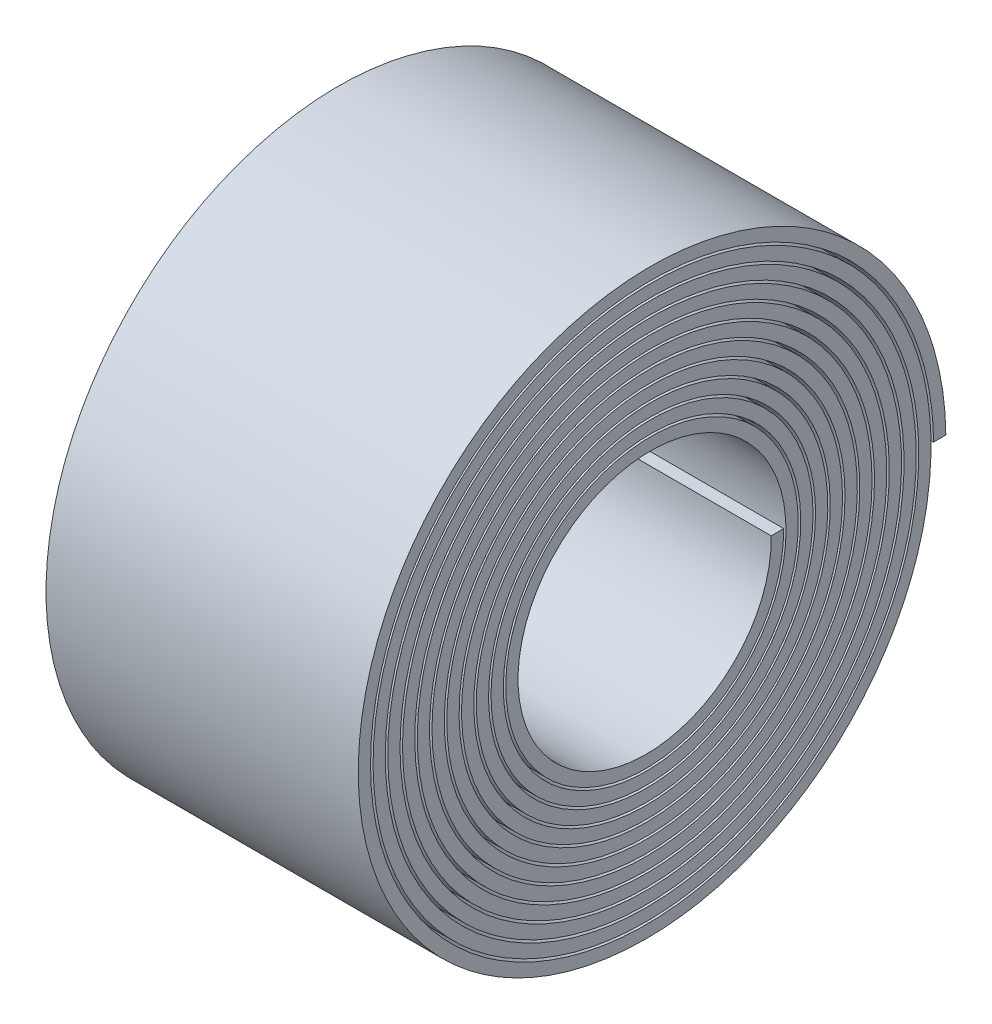
SolidWorks part; units mm, degrees
ref_plane "Front Plane" through (0, 0, 0) normal (0, 0, 1) x (1, 0, 0)
ref_plane "Top Plane" through (0, 0, 0) normal (0, 1, 0) x (1, 0, 0)
ref_plane "Right Plane" through (0, 0, 0) normal (1, 0, 0) x (0, 0, -1)
sketch "Sketch1" plane through (0, 0, 0) normal (1, 0, 0) x (0, 0, -1)
  circle A0 centre (0, 0) radius 2.5
  dimension "D1" = 5
curve "Helix/Spiral1"
sketch "Sketch2" plane through (0, 0, 0) normal (1, 0, 0) x (0, 0, -1)
  line L0 (2.5, 0) -> (2.75, 0.0048)
  line L2 (5.8, 0) -> (6.05, 0.0021)
  spline S0 degree 3 poles (-421.9366, -905.3575) (-57.6424, 57.3436) (7.9155, 8.7178) (1.9401, -1.6929) (1.6038, -2.0262) (0.8018, -2.4743) (0.3373, -2.5884) (-0.5902, -2.5601) (-1.0519, -2.4176) (-1.8406, -1.9113) (-2.1664, -1.5481) (-2.5866, -0.6999) (-2.6802, -0.2161) (-2.6036, 0.7366) (-2.4335, 1.2041) (-1.8725, 1.9894) (-1.4824, 2.3059) (-0.5889, 2.6946) (-0.0868, 2.7661) (0.8885, 2.6388) (1.3604, 2.4401) (2.1387, 1.8236) (2.444, 1.4066) (2.7978, 0.4689) (2.8456, -0.0505) (2.6652, -1.0457) (2.437, -1.5201) (1.7644, -2.2878) (1.3208, -2.58) (0.3402, -2.8954) (-0.1953, -2.9181) (-1.2075, -2.6823) (-1.6827, -2.424) (-2.4362, -1.6949) (-2.7134, -1.2249) (-2.9871, -0.203) (-2.9831, 0.3474) (-2.6898, 1.3734) (-2.4008, 1.8476) (-1.6149, 2.5831) (-1.119, 2.8434) (-0.0577, 3.072) (0.5063, 3.0399) (1.5429, 2.6873) (2.0141, 2.3671) (2.7278, 1.5245) (2.9693, 1.0032) (3.1497, -0.0956) (3.0882, -0.6716) (2.6745, -1.7154) (2.3227, -2.1817) (1.4237, -2.8698) (0.8778, -3.0906) (-0.2563, -3.2195) (-0.8428, -3.1274) (-1.8902, -2.651) (-2.3496, -2.2674) (-3.0082, -1.3126) (-3.2065, -0.7428) (-3.281, 0.4241) (-3.1571, 1.0194) (-2.6168, 2.0667) (-2.2011, 2.5172) (-1.1912, 3.1425) (-0.5985, 3.3164) (0.5985, 3.3336) (1.2009, 3.1767) (2.2444, 2.5714) (2.6838, 2.1236) (3.2719, 1.0598) (3.4197, 0.4451) (3.3768, -0.779) (3.186, -1.3868) (2.5147, -2.4224) (2.035, -2.8487) (0.9184, -3.3959) (0.2831, -3.5158) (-0.9652, -3.4101) (-1.5763, -3.1846) (-2.6001, -2.4467) (-3.0113, -1.9353) (-3.5136, -0.7674) (-3.604, -0.1126) (-3.4331, 1.1565) (-3.172, 1.769) (-2.3671, 2.7768) (-1.8243, 3.1707) (-0.6071, 3.6246) (0.0658, 3.6837) (1.3523, 3.4454) (1.9641, 3.148) (2.9519, 2.276) (3.3264, 1.7023) (3.728, 0.4376) (3.7545, -0.2517) (3.4465, -1.552) (3.1124, -2.1611) (2.1732, -3.1246) (1.5694, -3.4776) (0.2594, -3.8234) (-0.4448, -3.8157) (-1.755, -3.4362) (-2.3591, -3.0649) (-3.2941, -2.0589) (-3.6235, -1.4256) (-3.9101, -0.073) (-3.8667, 0.6444) (-3.414, 1.9607) (-3.0053, 2.5576) (-1.9331, 3.4598) (-1.2712, 3.7636) (0.1214, 3.9875) (0.8501, 3.9072) (2.1683, 3.3799) (2.7558, 2.9334) (3.6209, 1.7959) (3.897, 1.1064) (4.0551, -0.3232) (3.9367, -1.0613) (3.3334, -2.3772) (2.8492, -2.953) (1.6475, -3.7767) (0.9316, -4.0232) (-0.5319, -4.1123) (-1.2774, -3.9547) (-2.5866, -3.2743) (-3.1485, -2.7526) (-3.9265, -1.488) (-4.1414, -0.7469) (-4.1586, 0.7469) (-3.9607, 1.4977) (-3.2027, 2.7959) (-2.6435, 3.3414) (-1.3177, 4.0695) (-0.5529, 4.251) (0.9678, 4.1935) (1.7216, 3.9545) (3.0042, 3.1182) (3.531, 2.522) (4.2051, 1.1369) (4.3513, 0.35) (4.2166, -1.1938) (3.9357, -1.9485) (3.0209, -3.2108) (2.3882, -3.7167) (0.946, -4.3326) (0.1385, -4.4418) (-1.4244, -4.2274) (-2.1776, -3.9039) (-3.415, -2.9106) (-3.8975, -2.2421) (-4.4513, -0.7452) (-4.5218, 0.0811) (-4.2255, 1.6589) (-3.859, 2.4081) (-2.7875, 3.616) (-2.0839, 4.0728) (-0.535, 4.5606) (0.3082, 4.5908) (1.4994, 4.3057) (1.8841, 4.1566) (2.6009, 3.7605) (2.9328, 3.5135) (3.5195, 2.9389) (3.7743, 2.6113) (4.1877, 1.8991) (4.3463, 1.5144) (4.5553, 0.7154) (4.6057, 0.3011) (4.5939, -0.527) (4.5318, -0.9408) (4.299, -1.738) (4.1282, -2.1213) (3.69, -2.8295) (3.4224, -3.1543) (2.8094, -3.7215) (2.464, -3.9638) (1.7198, -4.348) (1.3212, -4.4898) (0.4992, -4.6621) (0.076, -4.6925) (-0.7644, -4.6392) (-1.1815, -4.5554) (-1.9795, -4.279) (-2.3602, -4.0864) (-3.0574, -3.6059) (-3.3738, -3.318) (-3.9191, -2.6671) (-4.1479, -2.3042) (-4.5007, -1.5294) (-4.6248, -1.1175) (-4.7585, -0.2744) (-4.7682, 0.1569) (-4.672, 1.0075) (-4.566, 1.4268) (-4.2455, 2.2231) (-4.0309, 2.5999) (-3.5082, 3.2837) (-3.2001, 3.5905) (-2.5121, 4.1115) (-2.1323, 4.3256) (-1.3281, 4.645) (-0.9038, 4.7503) (-0.0412, 4.8439) (0.397, 4.8322) (1.2556, 4.6919) (1.6759, 4.5634) (2.4681, 4.1982) (2.8398, 3.9616) (3.5077, 3.3969) (3.8037, 3.0688) (4.298, 2.3445) (4.4962, 1.9483) (4.7802, 1.1162) (4.8658, 0.6803) (4.9177, -0.1997) (4.8839, -0.6438) (4.6986, -1.508) (4.5472, -1.9281) (4.137, -2.7137) (3.8783, -3.0791) (3.2719, -3.7285) (2.9242, -4.0124) (2.1646, -4.4778) (1.7527, -4.6591) (0.8942, -4.9056) (0.4477, -4.9707) (-0.4477, -4.9793) (-0.8966, -4.9228) (-1.7641, -4.6916) (-2.1827, -4.517) (-2.9591, -4.0616) (-3.3169, -3.7809) (-3.9454, -3.1333) (-4.216, -2.7664) (-4.6501, -1.9726) (-4.8134, -1.5457) (-5.0206, -0.6626) (-5.0643, -0.2064) (-5.0282, 0.7022) (-4.9485, 1.1547) (-4.6707, 2.0231) (-4.4726, 2.4389) (-3.972, 3.2036) (-3.6694, 3.5525) (-2.9812, 4.1575) (-2.5956, 4.4136) (-1.7688, 4.8141) (-1.3277, 4.9585) (-0.4218, 5.1244) (0.043, 5.146) (0.9626, 5.064) (1.4175, 4.9605) (2.2841, 4.6354) (2.6959, 4.4138) (3.4463, 3.868) (3.7849, 3.5438) (4.364, 2.8157) (4.6044, 2.4119) (4.9693, 1.5536) (5.0936, 1.0992) (5.2166, 0.1724) (5.2152, -0.2999) (5.0862, -1.2282) (4.9585, -1.6841) (4.5857, -2.5465) (4.3404, -2.9529) (3.7496, -3.6864) (3.404, -4.0135) (2.637, -4.5641) (2.2157, -4.7877) (1.3274, -5.1147) (0.8606, -5.218) (-0.085, -5.2964) (-0.5637, -5.2714) (-1.4982, -5.0943) (-1.954, -4.9421) (-2.8095, -4.5211) (-3.2091, -4.2523) (-3.9231, -3.6168) (-4.2373, -3.2502) (-4.7571, -2.4454) (-4.9627, -2.0072) (-5.2497, -1.0907) (-5.3311, -0.6124) (-5.3633, 0.3498) (-5.3141, 0.8337) (-5.088, 1.7719) (-4.911, 2.2262) (-4.4417, 3.0721) (-4.1493, 3.4637) (-3.4697, 4.1554) (-3.0826, 4.4555) (-2.2411, 4.9421) (-1.7868, 5.1285) (-0.8438, 5.3736) (-0.3551, 5.4322) (0.6214, 5.4168) (1.1092, 5.3428) (2.0485, 5.0669) (2.5, 4.865) (3.3336, 4.3472) (3.7157, 4.0315) (4.3826, 3.3085) (4.6674, 2.9012) (5.1183, 2.0245) (5.2845, 1.555) (5.4857, 0.5874) (5.5208, 0.0894) (5.4565, -0.8991) (5.3571, -1.3896) (5.0307, -2.3273) (4.8037, -2.7745) (4.2377, -3.5931) (3.8987, -3.9644) (3.1331, -4.6039) (2.7064, -4.872) (1.7959, -5.285) (1.312, -5.4299) (0.322, -5.5855) (-0.1842, -5.5961) (-1.1821, -5.4817) (-1.6739, -5.3566) (-2.6074, -4.9793) (-3.049, -4.727) (-3.8498, -4.1129) (-4.2089, -3.7512) (-4.8184, -2.9439) (-5.0686, -2.4985) (-5.4414, -1.5557) (-5.5641, -1.0585) (-5.6722, -0.0482) (-5.6577, 0.4649) (-5.4921, 1.4698) (-5.3409, 1.9615) (-4.9123, 2.8879) (-4.6348, 3.3225) (-3.9731, 4.1028) (-3.5889, 4.4484) (-2.7411, 5.0252) (-2.2776, 5.2563) (-1.3045, 5.5868) (-0.795, 5.6862) (0.2334, 5.7453) (0.7521, 5.7051) (1.7612, 5.4873) (2.2515, 5.3097) (3.1681, 4.8296) (3.5942, 4.527) (4.3511, 3.8182) (4.6819, 3.412) (5.2235, 2.525) (5.4344, 2.0443) (11.0299, -17.545) (-82.1193, -65.6208) (-440.9328, 894.6492) knots -0.190622 -0.190622 -0.190622 -0.190622 0.007812 0.007812 0.015625 0.015625 0.023438 0.023438 0.03125 0.03125 0.039063 0.039063 0.046875 0.046875 0.054687 0.054687 0.0625 0.0625 0.070312 0.070312 0.078125 0.078125 0.085937 0.085937 0.09375 0.09375 0.101562 0.101562 0.109375 0.109375 0.117187 0.117187 0.125 0.125 0.132812 0.132812 0.140625 0.140625 0.148437 0.148437 0.15625 0.15625 0.164062 0.164062 0.171875 0.171875 0.179687 0.179687 0.1875 0.1875 0.195312 0.195312 0.203125 0.203125 0.210937 0.210937 0.21875 0.21875 0.226562 0.226562 0.234375 0.234375 0.242187 0.242187 0.25 0.25 0.257812 0.257812 0.265625 0.265625 0.273438 0.273438 0.28125 0.28125 0.289062 0.289062 0.296875 0.296875 0.304688 0.304688 0.3125 0.3125 0.320312 0.320312 0.328125 0.328125 0.335938 0.335938 0.34375 0.34375 0.351562 0.351562 0.359375 0.359375 0.367188 0.367188 0.375 0.375 0.382812 0.382812 0.390625 0.390625 0.398438 0.398438 0.40625 0.40625 0.414062 0.414062 0.421875 0.421875 0.429688 0.429688 0.4375 0.4375 0.445312 0.445312 0.453125 0.453125 0.460938 0.460938 0.46875 0.46875 0.476562 0.476562 0.484375 0.484375 0.492188 0.492188 0.5 0.5 0.507812 0.507812 0.515625 0.515625 0.523438 0.523438 0.53125 0.53125 0.539062 0.539062 0.546875 0.546875 0.554688 0.554688 0.5625 0.5625 0.570312 0.570312 0.578125 0.578125 0.585938 0.585938 0.59375 0.59375 0.601562 0.601562 0.609375 0.609375 0.617188 0.617188 0.621094 0.621094 0.625 0.625 0.628906 0.628906 0.632812 0.632812 0.636719 0.636719 0.640625 0.640625 0.644531 0.644531 0.648438 0.648438 0.652344 0.652344 0.65625 0.65625 0.660156 0.660156 0.664062 0.664062 0.667969 0.667969 0.671875 0.671875 0.675781 0.675781 0.679688 0.679688 0.683594 0.683594 0.6875 0.6875 0.691406 0.691406 0.695312 0.695312 0.699219 0.699219 0.703125 0.703125 0.707031 0.707031 0.710938 0.710938 0.714844 0.714844 0.71875 0.71875 0.722656 0.722656 0.726562 0.726562 0.730469 0.730469 0.734375 0.734375 0.738281 0.738281 0.742188 0.742188 0.746094 0.746094 0.75 0.75 0.753906 0.753906 0.757812 0.757812 0.761719 0.761719 0.765625 0.765625 0.769531 0.769531 0.773438 0.773438 0.777344 0.777344 0.78125 0.78125 0.785156 0.785156 0.789062 0.789062 0.792969 0.792969 0.796875 0.796875 0.800781 0.800781 0.804688 0.804688 0.808594 0.808594 0.8125 0.8125 0.816406 0.816406 0.820312 0.820312 0.824219 0.824219 0.828125 0.828125 0.832031 0.832031 0.835938 0.835938 0.839844 0.839844 0.84375 0.84375 0.847656 0.847656 0.851562 0.851562 0.855469 0.855469 0.859375 0.859375 0.863281 0.863281 0.867188 0.867188 0.871094 0.871094 0.875 0.875 0.878906 0.878906 0.882812 0.882812 0.886719 0.886719 0.890625 0.890625 0.894531 0.894531 0.898438 0.898438 0.902344 0.902344 0.90625 0.90625 0.910156 0.910156 0.914062 0.914062 0.917969 0.917969 0.921875 0.921875 0.925781 0.925781 0.929688 0.929688 0.933594 0.933594 0.9375 0.9375 0.941406 0.941406 0.945312 0.945312 0.949219 0.949219 0.953125 0.953125 0.957031 0.957031 0.960938 0.960938 0.964844 0.964844 0.96875 0.96875 0.972656 0.972656 0.976562 0.976562 0.980469 0.980469 0.984375 0.984375 0.988281 0.988281 0.992188 0.992188 0.996094 0.996094 1.144987 1.144987 1.144987 1.144987 only from (2.5, 0) to (5.8, 0) construction
  spline S1 degree 3 poles (2.5, 0) (2.5086, -0.45) (2.3928, -0.9042) (1.9401, -1.6929) (1.6038, -2.0262) (0.8018, -2.4743) (0.3373, -2.5884) (-0.5902, -2.5601) (-1.0519, -2.4176) (-1.8406, -1.9113) (-2.1664, -1.5481) (-2.5866, -0.6999) (-2.6802, -0.2161) (-2.6036, 0.7366) (-2.4335, 1.2041) (-1.8725, 1.9894) (-1.4824, 2.3059) (-0.5889, 2.6946) (-0.0868, 2.7661) (0.8885, 2.6388) (1.3604, 2.4401) (2.1387, 1.8236) (2.444, 1.4066) (2.7978, 0.4689) (2.8456, -0.0505) (2.6652, -1.0457) (2.437, -1.5201) (1.7644, -2.2878) (1.3208, -2.58) (0.3402, -2.8954) (-0.1953, -2.9181) (-1.2075, -2.6823) (-1.6827, -2.424) (-2.4362, -1.6949) (-2.7134, -1.2249) (-2.9871, -0.203) (-2.9831, 0.3474) (-2.6898, 1.3734) (-2.4008, 1.8476) (-1.6149, 2.5831) (-1.119, 2.8434) (-0.0577, 3.072) (0.5063, 3.0399) (1.5429, 2.6873) (2.0141, 2.3671) (2.7278, 1.5245) (2.9693, 1.0032) (3.1497, -0.0956) (3.0882, -0.6716) (2.6745, -1.7154) (2.3227, -2.1817) (1.4237, -2.8698) (0.8778, -3.0906) (-0.2563, -3.2195) (-0.8428, -3.1274) (-1.8902, -2.651) (-2.3496, -2.2674) (-3.0082, -1.3126) (-3.2065, -0.7428) (-3.281, 0.4241) (-3.1571, 1.0194) (-2.6168, 2.0667) (-2.2011, 2.5172) (-1.1912, 3.1425) (-0.5985, 3.3164) (0.5985, 3.3336) (1.2009, 3.1767) (2.2444, 2.5714) (2.6838, 2.1236) (3.2719, 1.0598) (3.4197, 0.4451) (3.3768, -0.779) (3.186, -1.3868) (2.5147, -2.4224) (2.035, -2.8487) (0.9184, -3.3959) (0.2831, -3.5158) (-0.9652, -3.4101) (-1.5763, -3.1846) (-2.6001, -2.4467) (-3.0113, -1.9353) (-3.5136, -0.7674) (-3.604, -0.1126) (-3.4331, 1.1565) (-3.172, 1.769) (-2.3671, 2.7768) (-1.8243, 3.1707) (-0.6071, 3.6246) (0.0658, 3.6837) (1.3523, 3.4454) (1.9641, 3.148) (2.9519, 2.276) (3.3264, 1.7023) (3.728, 0.4376) (3.7545, -0.2517) (3.4465, -1.552) (3.1124, -2.1611) (2.1732, -3.1246) (1.5694, -3.4776) (0.2594, -3.8234) (-0.4448, -3.8157) (-1.755, -3.4362) (-2.3591, -3.0649) (-3.2941, -2.0589) (-3.6235, -1.4256) (-3.9101, -0.073) (-3.8667, 0.6444) (-3.414, 1.9607) (-3.0053, 2.5576) (-1.9331, 3.4598) (-1.2712, 3.7636) (0.1214, 3.9875) (0.8501, 3.9072) (2.1683, 3.3799) (2.7558, 2.9334) (3.6209, 1.7959) (3.897, 1.1064) (4.0551, -0.3232) (3.9367, -1.0613) (3.3334, -2.3772) (2.8492, -2.953) (1.6475, -3.7767) (0.9316, -4.0232) (-0.5319, -4.1123) (-1.2774, -3.9547) (-2.5866, -3.2743) (-3.1485, -2.7526) (-3.9265, -1.488) (-4.1414, -0.7469) (-4.1586, 0.7469) (-3.9607, 1.4977) (-3.2027, 2.7959) (-2.6435, 3.3414) (-1.3177, 4.0695) (-0.5529, 4.251) (0.9678, 4.1935) (1.7216, 3.9545) (3.0042, 3.1182) (3.531, 2.522) (4.2051, 1.1369) (4.3513, 0.35) (4.2166, -1.1938) (3.9357, -1.9485) (3.0209, -3.2108) (2.3882, -3.7167) (0.946, -4.3326) (0.1385, -4.4418) (-1.4244, -4.2274) (-2.1776, -3.9039) (-3.415, -2.9106) (-3.8975, -2.2421) (-4.4513, -0.7452) (-4.5218, 0.0811) (-4.2255, 1.6589) (-3.859, 2.4081) (-2.7875, 3.616) (-2.0839, 4.0728) (-0.535, 4.5606) (0.3082, 4.5908) (1.4994, 4.3057) (1.8841, 4.1566) (2.6009, 3.7605) (2.9328, 3.5135) (3.5195, 2.9389) (3.7743, 2.6113) (4.1877, 1.8991) (4.3463, 1.5144) (4.5553, 0.7154) (4.6057, 0.3011) (4.5939, -0.527) (4.5318, -0.9408) (4.299, -1.738) (4.1282, -2.1213) (3.69, -2.8295) (3.4224, -3.1543) (2.8094, -3.7215) (2.464, -3.9638) (1.7198, -4.348) (1.3212, -4.4898) (0.4992, -4.6621) (0.076, -4.6925) (-0.7644, -4.6392) (-1.1815, -4.5554) (-1.9795, -4.279) (-2.3602, -4.0864) (-3.0574, -3.6059) (-3.3738, -3.318) (-3.9191, -2.6671) (-4.1479, -2.3042) (-4.5007, -1.5294) (-4.6248, -1.1175) (-4.7585, -0.2744) (-4.7682, 0.1569) (-4.672, 1.0075) (-4.566, 1.4268) (-4.2455, 2.2231) (-4.0309, 2.5999) (-3.5082, 3.2837) (-3.2001, 3.5905) (-2.5121, 4.1115) (-2.1323, 4.3256) (-1.3281, 4.645) (-0.9038, 4.7503) (-0.0412, 4.8439) (0.397, 4.8322) (1.2556, 4.6919) (1.6759, 4.5634) (2.4681, 4.1982) (2.8398, 3.9616) (3.5077, 3.3969) (3.8037, 3.0688) (4.298, 2.3445) (4.4962, 1.9483) (4.7802, 1.1162) (4.8658, 0.6803) (4.9177, -0.1997) (4.8839, -0.6438) (4.6986, -1.508) (4.5472, -1.9281) (4.137, -2.7137) (3.8783, -3.0791) (3.2719, -3.7285) (2.9242, -4.0124) (2.1646, -4.4778) (1.7527, -4.6591) (0.8942, -4.9056) (0.4477, -4.9707) (-0.4477, -4.9793) (-0.8966, -4.9228) (-1.7641, -4.6916) (-2.1827, -4.517) (-2.9591, -4.0616) (-3.3169, -3.7809) (-3.9454, -3.1333) (-4.216, -2.7664) (-4.6501, -1.9726) (-4.8134, -1.5457) (-5.0206, -0.6626) (-5.0643, -0.2064) (-5.0282, 0.7022) (-4.9485, 1.1547) (-4.6707, 2.0231) (-4.4726, 2.4389) (-3.972, 3.2036) (-3.6694, 3.5525) (-2.9812, 4.1575) (-2.5956, 4.4136) (-1.7688, 4.8141) (-1.3277, 4.9585) (-0.4218, 5.1244) (0.043, 5.146) (0.9626, 5.064) (1.4175, 4.9605) (2.2841, 4.6354) (2.6959, 4.4138) (3.4463, 3.868) (3.7849, 3.5438) (4.364, 2.8157) (4.6044, 2.4119) (4.9693, 1.5536) (5.0936, 1.0992) (5.2166, 0.1724) (5.2152, -0.2999) (5.0862, -1.2282) (4.9585, -1.6841) (4.5857, -2.5465) (4.3404, -2.9529) (3.7496, -3.6864) (3.404, -4.0135) (2.637, -4.5641) (2.2157, -4.7877) (1.3274, -5.1147) (0.8606, -5.218) (-0.085, -5.2964) (-0.5637, -5.2714) (-1.4982, -5.0943) (-1.954, -4.9421) (-2.8095, -4.5211) (-3.2091, -4.2523) (-3.9231, -3.6168) (-4.2373, -3.2502) (-4.7571, -2.4454) (-4.9627, -2.0072) (-5.2497, -1.0907) (-5.3311, -0.6124) (-5.3633, 0.3498) (-5.3141, 0.8337) (-5.088, 1.7719) (-4.911, 2.2262) (-4.4417, 3.0721) (-4.1493, 3.4637) (-3.4697, 4.1554) (-3.0826, 4.4555) (-2.2411, 4.9421) (-1.7868, 5.1285) (-0.8438, 5.3736) (-0.3551, 5.4322) (0.6214, 5.4168) (1.1092, 5.3428) (2.0485, 5.0669) (2.5, 4.865) (3.3336, 4.3472) (3.7157, 4.0315) (4.3826, 3.3085) (4.6674, 2.9012) (5.1183, 2.0245) (5.2845, 1.555) (5.4857, 0.5874) (5.5208, 0.0894) (5.4565, -0.8991) (5.3571, -1.3896) (5.0307, -2.3273) (4.8037, -2.7745) (4.2377, -3.5931) (3.8987, -3.9644) (3.1331, -4.6039) (2.7064, -4.872) (1.7959, -5.285) (1.312, -5.4299) (0.322, -5.5855) (-0.1842, -5.5961) (-1.1821, -5.4817) (-1.6739, -5.3566) (-2.6074, -4.9793) (-3.049, -4.727) (-3.8498, -4.1129) (-4.2089, -3.7512) (-4.8184, -2.9439) (-5.0686, -2.4985) (-5.4414, -1.5557) (-5.5641, -1.0585) (-5.6722, -0.0482) (-5.6577, 0.4649) (-5.4921, 1.4698) (-5.3409, 1.9615) (-4.9123, 2.8879) (-4.6348, 3.3225) (-3.9731, 4.1028) (-3.5889, 4.4484) (-2.7411, 5.0252) (-2.2776, 5.2563) (-1.3045, 5.5868) (-0.795, 5.6862) (0.2334, 5.7453) (0.7521, 5.7051) (1.7612, 5.4873) (2.2515, 5.3097) (3.1681, 4.8296) (3.5942, 4.527) (4.3511, 3.8182) (4.6819, 3.412) (5.2235, 2.525) (5.4344, 2.0443) (5.7205, 1.0427) (5.7957, 0.522) (5.8, 0) knots 0 0 0 0 0.007812 0.007812 0.015625 0.015625 0.023438 0.023438 0.03125 0.03125 0.039063 0.039063 0.046875 0.046875 0.054687 0.054687 0.0625 0.0625 0.070312 0.070312 0.078125 0.078125 0.085937 0.085937 0.09375 0.09375 0.101562 0.101562 0.109375 0.109375 0.117187 0.117187 0.125 0.125 0.132812 0.132812 0.140625 0.140625 0.148437 0.148437 0.15625 0.15625 0.164062 0.164062 0.171875 0.171875 0.179687 0.179687 0.1875 0.1875 0.195312 0.195312 0.203125 0.203125 0.210937 0.210937 0.21875 0.21875 0.226562 0.226562 0.234375 0.234375 0.242187 0.242187 0.25 0.25 0.257812 0.257812 0.265625 0.265625 0.273438 0.273438 0.28125 0.28125 0.289062 0.289062 0.296875 0.296875 0.304688 0.304688 0.3125 0.3125 0.320312 0.320312 0.328125 0.328125 0.335938 0.335938 0.34375 0.34375 0.351562 0.351562 0.359375 0.359375 0.367188 0.367188 0.375 0.375 0.382812 0.382812 0.390625 0.390625 0.398438 0.398438 0.40625 0.40625 0.414062 0.414062 0.421875 0.421875 0.429688 0.429688 0.4375 0.4375 0.445312 0.445312 0.453125 0.453125 0.460938 0.460938 0.46875 0.46875 0.476562 0.476562 0.484375 0.484375 0.492188 0.492188 0.5 0.5 0.507812 0.507812 0.515625 0.515625 0.523438 0.523438 0.53125 0.53125 0.539062 0.539062 0.546875 0.546875 0.554688 0.554688 0.5625 0.5625 0.570312 0.570312 0.578125 0.578125 0.585938 0.585938 0.59375 0.59375 0.601562 0.601562 0.609375 0.609375 0.617188 0.617188 0.621094 0.621094 0.625 0.625 0.628906 0.628906 0.632812 0.632812 0.636719 0.636719 0.640625 0.640625 0.644531 0.644531 0.648438 0.648438 0.652344 0.652344 0.65625 0.65625 0.660156 0.660156 0.664062 0.664062 0.667969 0.667969 0.671875 0.671875 0.675781 0.675781 0.679688 0.679688 0.683594 0.683594 0.6875 0.6875 0.691406 0.691406 0.695312 0.695312 0.699219 0.699219 0.703125 0.703125 0.707031 0.707031 0.710938 0.710938 0.714844 0.714844 0.71875 0.71875 0.722656 0.722656 0.726562 0.726562 0.730469 0.730469 0.734375 0.734375 0.738281 0.738281 0.742188 0.742188 0.746094 0.746094 0.75 0.75 0.753906 0.753906 0.757812 0.757812 0.761719 0.761719 0.765625 0.765625 0.769531 0.769531 0.773438 0.773438 0.777344 0.777344 0.78125 0.78125 0.785156 0.785156 0.789062 0.789062 0.792969 0.792969 0.796875 0.796875 0.800781 0.800781 0.804688 0.804688 0.808594 0.808594 0.8125 0.8125 0.816406 0.816406 0.820312 0.820312 0.824219 0.824219 0.828125 0.828125 0.832031 0.832031 0.835938 0.835938 0.839844 0.839844 0.84375 0.84375 0.847656 0.847656 0.851562 0.851562 0.855469 0.855469 0.859375 0.859375 0.863281 0.863281 0.867188 0.867188 0.871094 0.871094 0.875 0.875 0.878906 0.878906 0.882812 0.882812 0.886719 0.886719 0.890625 0.890625 0.894531 0.894531 0.898438 0.898438 0.902344 0.902344 0.90625 0.90625 0.910156 0.910156 0.914062 0.914062 0.917969 0.917969 0.921875 0.921875 0.925781 0.925781 0.929688 0.929688 0.933594 0.933594 0.9375 0.9375 0.941406 0.941406 0.945312 0.945312 0.949219 0.949219 0.953125 0.953125 0.957031 0.957031 0.960938 0.960938 0.964844 0.964844 0.96875 0.96875 0.972656 0.972656 0.976562 0.976562 0.980469 0.980469 0.984375 0.984375 0.988281 0.988281 0.992188 0.992188 0.996094 0.996094 1 1 1 1
  spline S2 degree 1 poles (2.75, 0.0048) (6.05, 0.0021) knots 0 0 1 1 construction
  spline S3 degree 3 poles (2.75, 0.0048) (2.7593, -0.4865) (2.5044, -1.4912) (1.395, -2.5887) (-0.1359, -2.9651) (-1.656, -2.4957) (-2.7279, -1.3009) (-3.0355, 0.2893) (-2.4766, 1.8249) (-1.1964, 2.8635) (0.45, 3.098) (1.9958, 2.4468) (2.9953, 1.0817) (3.1518, -0.6174) (2.406, -2.1681) (0.9569, -3.1225) (-0.7912, -3.1964) (-2.3411, -2.354) (-3.2445, -0.8221) (-3.2314, 0.9707) (-2.2908, 2.514) (-0.6777, 3.3605) (1.1556, 3.2563) (2.6862, 2.2161) (3.4701, 0.5238) (3.2706, -1.3451) (2.1299, -2.857) (0.3607, -3.5724) (-1.5388, -3.2741) (-3.0256, -2.0322) (-3.6669, -0.1889) (-3.2662, 1.7359) (-1.9229, 3.1914) (-0.0086, 3.753) (1.9359, 3.2467) (3.3535, 1.8022) (3.83, -0.1796) (3.2152, -2.1381) (1.6701, -3.5113) (-0.3753, -3.8973) (-2.3417, -3.1716) (-3.6641, -1.5268) (-3.9545, 0.5781) (-3.1156, 2.5461) (-1.3725, 3.8111) (0.7874, 4.001) (2.7505, 3.047) (3.9516, 1.2073) (4.0363, -1.0025) (2.9658, -2.9541) (1.0316, -4.0848) (-1.223, -4.0599) (-3.1563, -2.8717) (-4.2102, -0.8457) (-4.0714, 1.4482) (-2.7648, 3.3562) (-0.65, 4.3269) (1.6773, 4.0705) (3.5531, 2.6451) (4.4344, 0.4448) (4.0566, -1.9098) (2.5127, -3.7462) (0.2306, -4.532) (-2.1449, -4.0296) (-3.9346, -2.3675) (-4.619, -0.0079) (-3.9891, 2.3818) (-2.2098, 4.1177) (0.2228, 4.695) (2.6198, 3.9349) (4.2946, 2.0398) (4.7592, -0.4609) (3.8668, -2.8582) (1.8576, -4.4645) (-0.7059, -4.8111) (-3.096, -3.7847) (-4.6267, -1.6636) (-4.8503, 0.957) (-3.6883, 3.3326) (-1.4581, 4.7805) (1.2136, 4.8763) (3.567, 3.5777) (4.9251, 1.2415) (4.8885, -1.475) (3.4529, -3.7984) (1.0141, -5.0597) (-1.7405, -4.8867) (-4.0261, -3.3138) (-5.1837, -0.7765) (-4.8704, 2.0093) (-3.1606, 4.2491) (-0.5292, 5.2964) (2.2806, 4.8393) (4.4666, 2.9934) (5.397, 0.2726) (4.7932, -2.5536) (2.8123, -4.6777) (0.0074, -5.4851) (-2.8275, -4.7317) (-4.8817, -2.6177) (-5.56, 0.2658) (-4.6548, 3.1014) (-2.4097, 5.0777) (0.5463, 5.621) (3.3745, 4.5622) (5.2648, 2.1887) (5.6678, -0.8334) (4.4539, -3.6458) (1.955, -5.4423) (-1.1264, -5.6997) (-3.9145, -4.3298) (-5.6094, -1.7091) (-5.7163, 1.4244) (-4.1899, 4.1797) (-1.4515, 5.7653) (1.7268, 5.7172) (4.4404, 4.0342) (5.9092, 1.1827) (5.702, -2.0326) (3.863, -4.6958) (0.9032, -6.0405) (-2.3411, -5.6704) (-4.9449, -3.6762) (-6.1583, -0.6137) (-5.6221, 2.6513) (-3.4743, 5.1867) (-0.3147, 6.2626) (2.9622, 5.555) (5.4207, 3.2642) (6.0412, 1.0755) (6.05, 0.0021) knots 0 0 0 0 0.007812 0.015625 0.023438 0.03125 0.039062 0.046875 0.054688 0.0625 0.070312 0.078125 0.085938 0.09375 0.101562 0.109375 0.117188 0.125 0.132812 0.140625 0.148438 0.15625 0.164062 0.171875 0.179688 0.1875 0.195312 0.203125 0.210938 0.21875 0.226562 0.234375 0.242188 0.25 0.257812 0.265625 0.273438 0.28125 0.289062 0.296875 0.304688 0.3125 0.320312 0.328125 0.335938 0.34375 0.351562 0.359375 0.367188 0.375 0.382812 0.390625 0.398438 0.40625 0.414062 0.421875 0.429688 0.4375 0.445312 0.453125 0.460938 0.46875 0.476562 0.484375 0.492188 0.5 0.507812 0.515625 0.523438 0.53125 0.539062 0.546875 0.554688 0.5625 0.570312 0.578125 0.585938 0.59375 0.601562 0.609375 0.617188 0.625 0.632812 0.640625 0.648438 0.65625 0.664062 0.671875 0.679688 0.6875 0.695312 0.703125 0.710938 0.71875 0.726562 0.734375 0.742188 0.75 0.757812 0.765625 0.773438 0.78125 0.789062 0.796875 0.804688 0.8125 0.820312 0.828125 0.835938 0.84375 0.851562 0.859375 0.867188 0.875 0.882812 0.890625 0.898438 0.90625 0.914062 0.921875 0.929688 0.9375 0.945312 0.953125 0.960938 0.96875 0.976562 0.984375 0.992188 1 1 1 1
  dimension "D1" = 0.25
extrude "Boss-Extrude1" add sketch "Sketch2" along normal mid plane 6.35
sketch "Sketch3" plane through (0, 0, 0) normal (1, 0, 0) x (0, 0, -1)
  circle A0 centre (0, 0) radius 6.05 construction
